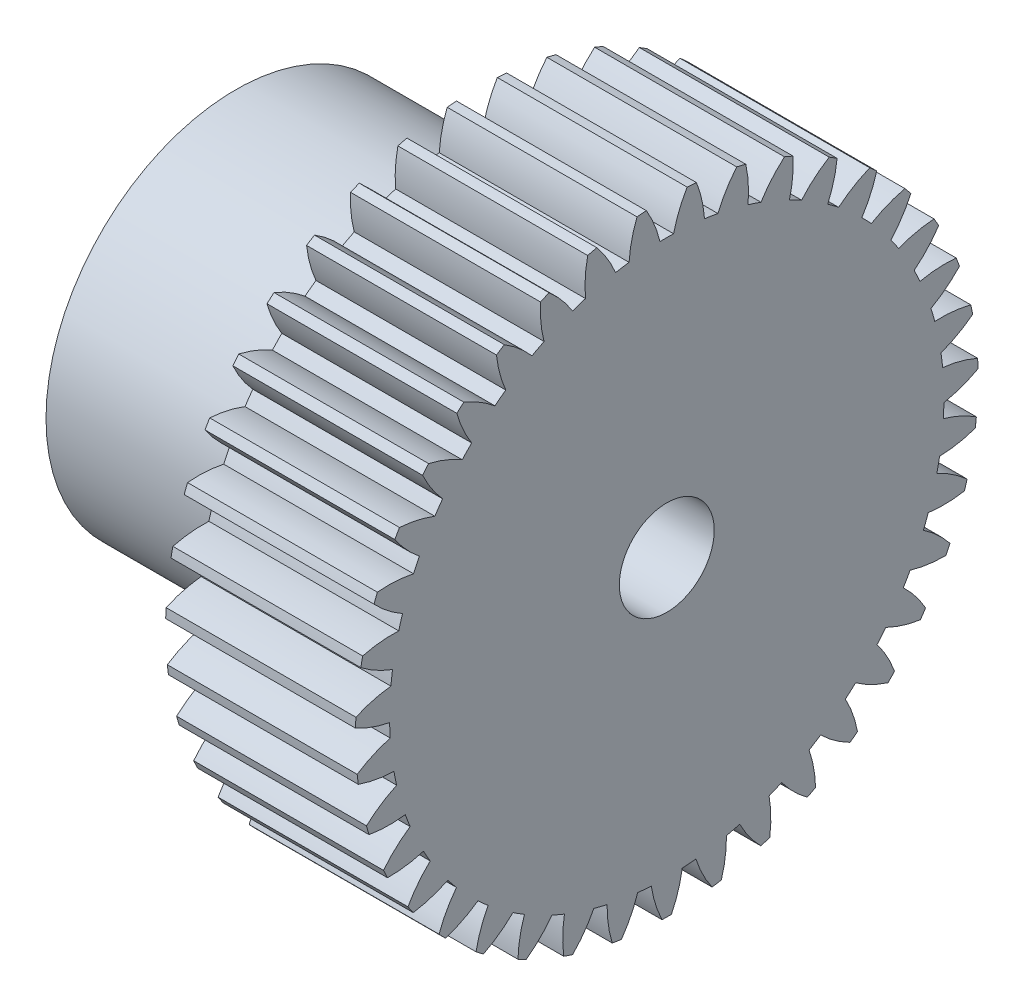
SolidWorks part; units mm, degrees
ref_plane "Plane1" through (0, 0, 0) normal (0, 0, 1) x (1, 0, 0)
ref_plane "Plane2" through (0, 0, 0) normal (0, 1, 0) x (1, 0, 0)
ref_plane "Plane3" through (0, 0, 0) normal (1, 0, 0) x (0, 0, -1)
sketch "HoldingSke" plane through (0, 0, 0) normal (0, 1, 0) x (1, 0, 0)
  line L0 (0, 0) -> (0.9714, -0.7867)
  line L1 (-15, 0) -> (100, 0) construction
  line L2 (0, 0) -> (-2.1039, 2.3779)
  line L3 (0, 0) -> (-11.863, 4.5341)
  line L4 (0, 0) -> (6.7114, 5.4348)
  line L5 (0, 0) -> (-9.3695, -3.4946)
  line L6 (0, 0) -> (-8.2896, -5.593)
  line L7 (-2.1039, 2.3779) -> (0.0486, 12.1435)
  line L8 (-76.2, 54.61) -> (-75.3, 54.61)
  line L9 (-71.009, 38.7566) -> (-53.1078, 45.2721)
  line L10 (-76.2, 71.12) -> (104.1128, 71.12)
  line L11 (0, 0) -> (-10, 0)
  line L12 (-76.2, 101.6) -> (-76.17, 101.6)
  line L13 (24.9733, 27.94) -> (52.9518, 28.4284)
  line L14 (24.9733, 27.94) -> (24.9743, 27.94)
  line L15 (24.9733, 27.94) -> (100.4006, 29.5858)
  line L16 (-63.627, -0.8) -> (-12.827, -0.8)
  circle A0 centre (0, 0) radius 2.5
  circle A1 centre (0, 0) radius 10
  circle A2 centre (0, 0) radius 10
  circle A3 centre (0, 0) radius 2.5
  dimension "Num_teeth" = 39
  dimension "Pitch_radius" = 180.3128
  dimension "Width" = 10
  dimension "Thickness" = 10
sketch "BasProSke" plane through (0, 0, 0) normal (0, 1, 0) x (1, 0, 0)
  line L0 (-10, 0) -> (60, 0) construction
  line L1 (0, 0) -> (0, 16.4)
  line L2 (0, 0) -> (10, 0)
  line L3 (10, 0) -> (10, 16.4)
  line L4 (10, 16.4) -> (0, 16.4)
  dimension "Thickness" = 10
  dimension "Diameter" = 32.8
revolve "Base-Revolve" add sketch "BasProSke" angle 360 about L0
sketch "TooCutSke" plane through (0, 0, 0) normal (1, 0, 0) x (0, 0, -1)
  line L1 (0, 0) -> (0, 107) construction
  line L2 (0, 0) -> (-0.6806, 15.5851) construction
  line L3 (0, 0) -> (-2.5088, 31.0776) construction
  line L4 (-0.6806, 15.5851) -> (-1.2544, 15.5388) construction
  arc A0 (0.3593, 14.5946) -> (-0.3593, 14.5946) centre (0, 0) ccw
  arc A1 (1.0886, 16.3893) -> (-1.0886, 16.3893) centre (0, 0) ccw
  circle A2 centre (0, 0) radius 15.6 construction
  circle A3 centre (0, 0) radius 14.6592 construction
  arc A4 (-0.3593, 14.5946) -> (-1.0886, 16.3893) centre (-6.4349, 13.1714) ccw
  arc A5 (1.0886, 16.3893) -> (0.3593, 14.5946) centre (6.4349, 13.1714) ccw
extrude "ToothCut" cut sketch "TooCutSke" along normal through all
fillet "Breaks" [suppressed] radius 0.016 tangent propagation no
fillet "RootFillets" [suppressed] radius 0.201
pattern_circular "TeethCuts" count 39 every 9.231 about axis through (-10, 0, 0) along (1, 0, 0) of "ToothCut", "RootFillets", "Breaks"
sketch "HubNeaOneSke" plane through (0, 0, 0) normal (-1, 0, 0) x (0, 0, 1)
  circle A0 centre (0, 0) radius 10
  dimension "Diameter" = 20
extrude "HubNearOne" add sketch "HubNeaOneSke" along normal blind 12.7001
sketch "HubNeaBotSke" plane through (0, 0, 0) normal (-1, 0, 0) x (0, 0, 1)
  circle A0 centre (0, 0) radius 10
  dimension "Diameter" = 20
extrude "HubNearBoth" [suppressed] add sketch "HubNeaBotSke" along normal blind 6.35
ref_plane "FarPln" through (10, 0, 0) normal (1, 0, 0) x (0, 0, -1)
sketch "HubFarSke" plane through (10, 0, 0) normal (1, 0, 0) x (0, 0, -1)
  circle A0 centre (0, 0) radius 10
  dimension "Diameter" = 20
extrude "HubFar" [suppressed] add sketch "HubFarSke" along normal blind 6.35
sketch "BorSke" plane through (0, 0, 0) normal (1, 0, 0) x (0, 0, -1)
  circle A0 centre (0, 0) radius 2.5
  dimension "Diameter" = 5
extrude "Bore" cut sketch "BorSke" along normal through all both and the other way through all
sketch "KeySke" plane through (0, 0, 0) normal (1, 0, 0) x (0, 0, -1)
  line L0 (-1, 0) -> (-1, 3.4)
  line L1 (-1, 3.4) -> (1, 3.4)
  line L2 (1, 3.4) -> (1, 0)
  line L3 (0, 0) -> (0, 34) construction
  line L4 (-1, 0) -> (1, 0)
  dimension "Width" = 2
extrude "Keyway" [suppressed] cut sketch "KeySke" along normal mid plane 20.0001
pattern_circular "Keyway2" [suppressed] count 2 every 90 about axis through (-10, 0, 0) along (1, 0, 0) reverse direction yes
ref_plane "Plane4" through (0, 0, -10) normal (0, 0, -1) x (-1, 0, 0)
sketch "Sketch1" plane through (0, 0, -10) normal (0, 0, -1) x (-1, 0, 0)
  line L0 (6.35, 0) -> (6.35, -6.7791) construction
  line L1 (12.7001, -10) -> (12.7001, 10) construction
  line L2 (0, -10) -> (0, 10) construction
  line L3 (50, 0) -> (-50, 0) construction
  circle A0 centre (6.35, 0) radius 2.65
  circle A1 centre (6.35, 0) radius 1.6
  dimension "D1" = 5.3
  dimension "D2" = 3.2
extrude "Cut-Extrude1" cut sketch "Sketch1" against normal blind 5
extrude "Cut-Extrude2" cut sketch "Sketch1<2>" against normal blind 10 contours A1 L0 | L0 A1 region at (-5.2507, 1.0994, -10)
sketch "Sketch1<2>" plane through (0, 0, -10) normal (0, 0, -1) x (-1, 0, 0) same geometry as "Sketch1"
equation "' \"Module@HoldingSke\" = 6.35"
equation "' \"Num_teeth@HoldingSke\" = 12"
equation "' \"Ap@HoldingSke\" =  20"
equation "' \"Ap@HoldingSke\" = 20"
equation "' \"Width@HoldingSke\" = 0.5 * 25.4"
equation "' \"Hub_dia@HoldingSke\"= 1 * 25.4"
equation "' \"Hub_dia@HoldingSke\" = 1 * 25.4"
equation "' \"Overall_len@HoldingSke\" = 1.0 * 25.4"
equation "' \"Bore@HoldingSke\" = 0.75 * 25.4"
equation "' \"T_dim@HoldingSke\" = 0.1 * 25.4"
equation "' \"Width@KeySke\" = 0.25 * 25.4"
equation "' \"Show_teeth@HoldingSke\" = 13"
equation "' \"Backlash@HoldingSke\" = 0.009 * 25.4"
equation "' \"Addendum_fac@HoldingSke\" = 1.0"
equation "' \"Dedendum_fac@HoldingSke\" = 1.25"
equation "' \"Dedendum_add@HoldingSke\" = 0.00005 * 25.4"
equation "' \"Clearance_fac@HoldingSke\" = 0.25"
equation "\"Pitch@HoldingSke\" = 1 / \"Module@HoldingSke\""
equation "\"Overcut_dia@TooCutSke\" = (\"Num_teeth@HoldingSke\" + 2 * \"Addendum_fac@HoldingSke\") / \"Pitch@HoldingSke\" + 0.002 * 25.4"
equation "\"Pitch_dia@TooCutSke\" = \"Num_teeth@HoldingSke\" / \"Pitch@HoldingSke\""
equation "\"Base_dia@TooCutSke\" = \"Num_teeth@HoldingSke\" / \"Pitch@HoldingSke\" * cos((\"Ap@HoldingSke\"  * 3.14159265 / 180))"
equation "\"Root_dia@TooCutSke\" = (\"Num_teeth@HoldingSke\" + 2) / \"Pitch@HoldingSke\" - 2 * (\"Addendum_fac@HoldingSke\" + \"Dedendum_fac@HoldingSke\") / \"Pitch@HoldingSke\" - \"Dedendum_add@HoldingSke\" * 2"
equation "\"Half_ang@TooCutSke\" = 180 / \"Num_teeth@HoldingSke\""
equation "\"Half_CT@TooCutSke\" = \"Num_teeth@HoldingSke\" / \"Pitch@HoldingSke\" * sin((3.14159265 / 2 / \"Num_teeth@HoldingSke\")) / 2 - 7 * \"Backlash@HoldingSke\" / 4"
equation "\"Flank_rad@TooCutSke\" = \"Num_teeth@HoldingSke\" / \"Pitch@HoldingSke\" / 5"
equation "\"Radius@RootFillets\" = \"Clearance_fac@HoldingSke\" / \"Pitch@HoldingSke\" + \"Dedendum_add@HoldingSke\""
equation "\"Break_rad@Breaks\" = 0.02 / \"Pitch@HoldingSke\""
equation "\"Thickness@HoldingSke\" = \"Width@HoldingSke\""
equation "\"OAL@HoldingSke\" = \"Thickness@HoldingSke\""
equation "\"MHD@HoldingSke\" = (\"Num_teeth@HoldingSke\" + 2) / \"Pitch@HoldingSke\" - 2 * (\"Addendum_fac@HoldingSke\" + \"Dedendum_fac@HoldingSke\")  / \"Pitch@HoldingSke\" - \"Dedendum_add@HoldingSke\" * 2"
equation "\"MBD@HoldingSke\" = (\"Num_teeth@HoldingSke\" + 2) / \"Pitch@HoldingSke\" - 2 * (\"Addendum_fac@HoldingSke\" + \"Dedendum_fac@HoldingSke\")  / \"Pitch@HoldingSke\" - \"Dedendum_add@HoldingSke\" * 2 - 0.002 * 25.4"
equation "\"MHD@HoldingSke\" = ((sgn( \"MHD@HoldingSke\" - \"Hub_dia@HoldingSke\" )-1)*( \"MHD@HoldingSke\" - \"Hub_dia@HoldingSke\" ))/-2+ \"Hub_dia@HoldingSke\""
equation "\"MBD@HoldingSke\" = ((sgn( \"MBD@HoldingSke\" - \"Bore@HoldingSke\" )-1)*( \"MBD@HoldingSke\" - \"Bore@HoldingSke\" ))/-2+ \"Bore@HoldingSke\""
equation "\"OAL@HoldingSke\" = ((sgn( \"OAL@HoldingSke\" - \"Overall_len@HoldingSke\" )+1)*( \"OAL@HoldingSke\" - \"Overall_len@HoldingSke\" ))/2 + \"Overall_len@HoldingSke\" + 0.000002 * 25.4"
equation "\"Num_teeth@TeethCuts\" = int( \"Show_teeth@HoldingSke\" ) + 1"
equation "\"Num_teeth@TeethCuts\" = ((sgn( \"Num_teeth@TeethCuts\" - \"Num_teeth@HoldingSke\" )-1)*( \"Num_teeth@TeethCuts\" - \"Num_teeth@HoldingSke\" ))/-2+ \"Num_teeth@HoldingSke\""
equation "\"Num_teeth@TeethCuts\" = ((sgn( \"Num_teeth@TeethCuts\" - 2.0)+1)*( \"Num_teeth@TeethCuts\" - 2.0))/2 +2.0"
equation "\"Angle@TeethCuts\" = 360.0 / \"Num_teeth@HoldingSke\""
equation "\"Diameter@BasProSke\" = (\"Num_teeth@HoldingSke\" + 2 * \"Addendum_fac@HoldingSke\") / \"Pitch@HoldingSke\""
equation "\"Thickness@BasProSke\"  = \"Thickness@HoldingSke\""
equation "' \"Fillet_rad@BasProSke\" =  \"Thickness@HoldingSke\" * 0.05"
equation "' \"Fillet_rad@BasProSke\" = \"Thickness@HoldingSke\" * 0.05"
equation "\"MHD@HoldingSke\" = ((sgn( \"MHD@HoldingSke\" - \"Root_dia@TooCutSke\" )-1)*( \"MHD@HoldingSke\" - \"Root_dia@TooCutSke\" ))/-2+ \"Root_dia@TooCutSke\""
equation "\"Diameter@HubNeaOneSke\" = \"MHD@HoldingSke\""
equation "\"Length@HubNearOne\" = \"OAL@HoldingSke\" - \"Thickness@BasProSke\""
equation "\"Diameter@HubNeaBotSke\" = \"MHD@HoldingSke\""
equation "\"Length@HubNearBoth\" = ( \"OAL@HoldingSke\" - \"Thickness@BasProSke\" ) / 2.0"
equation "\"Thickness@FarPln\" = \"Thickness@BasProSke\""
equation "\"Diameter@HubFarSke\" = \"MHD@HoldingSke\""
equation "\"Length@HubFar\" = ( \"OAL@HoldingSke\" - \"Thickness@BasProSke\" ) / 2.0"
equation "\"Diameter@BorSke\" = \"MBD@HoldingSke\""
equation "\"D1@Keyway\" = \"OAL@HoldingSke\" * 2.0"
equation "\"Offset@KeySke\" = \"T_dim@HoldingSke\" + \"MBD@HoldingSke\" / 2.0"
